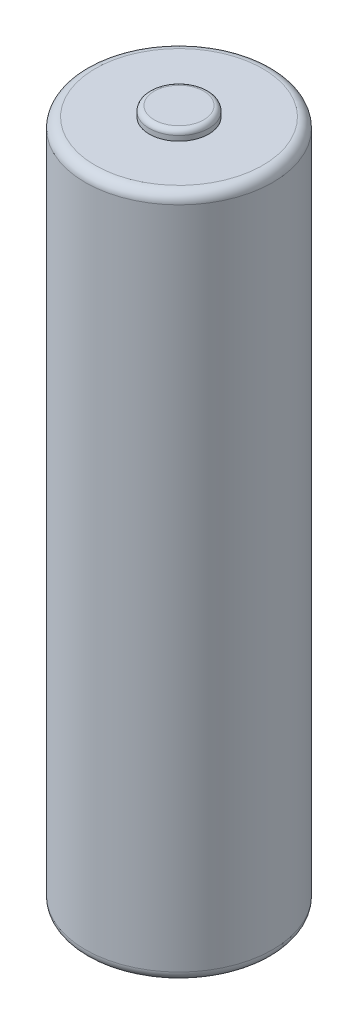
SolidWorks part; units mm, degrees
ref_plane "Front Plane" through (0, 0, 0) normal (0, 0, 1) x (1, 0, 0)
ref_plane "Top Plane" through (0, 0, 0) normal (0, 1, 0) x (1, 0, 0)
ref_plane "Right Plane" through (0, 0, 0) normal (1, 0, 0) x (0, 0, -1)
sketch "Sketch1" plane through (0, 0, 0) normal (0, 1, 0) x (1, 0, 0)
  circle A0 centre (0, 0) radius 9.45
  dimension "D1" = 18.9
extrude "Boss-Extrude1" add sketch "Sketch1" along normal blind 35 and the other way blind 35
sketch "Sketch2" plane through (0, 35, 0) normal (0, 1, 0) x (1, 0, 0)
  circle A0 centre (0, 0) radius 3
  circle A1 centre (0, 0) radius 9.45
  circle A2 centre (0, 0) radius 9.45 construction
  dimension "D1" = 6
extrude "Cut-Extrude1" cut sketch "Sketch2" against normal blind 1
fillet "Fillet1" radius 0.5 1 edges at (0, 35, 3)
fillet "Fillet2" radius 1 2 edges at (0, -35, 9.45) (0, 34, 9.45)
